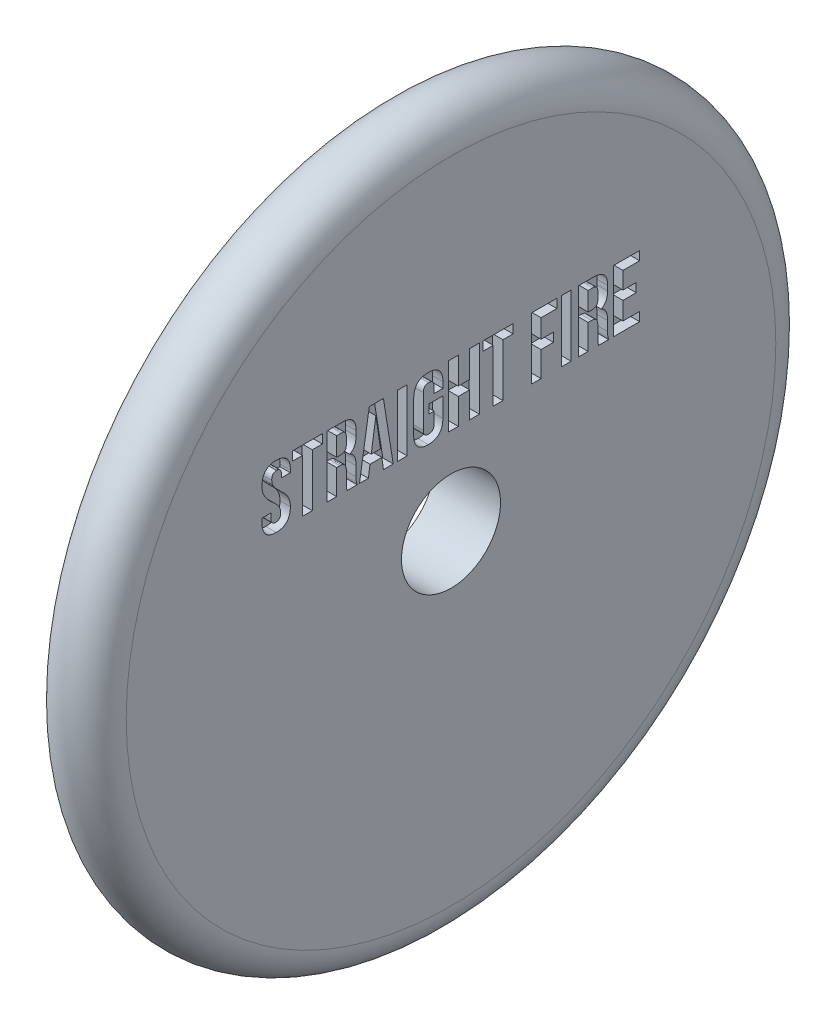
SolidWorks part; units mm, degrees
ref_plane "Front Plane" through (0, 0, 0) normal (0, 0, 1) x (1, 0, 0)
ref_plane "Top Plane" through (0, 0, 0) normal (0, 1, 0) x (1, 0, 0)
ref_plane "Right Plane" through (0, 0, 0) normal (1, 0, 0) x (0, 0, -1)
sketch "Sketch2" plane through (0, 0, 0) normal (0, 1, 0) x (1, 0, 0)
  line L0 (-9.525, 34.925) -> (9.525, 34.925) construction
  line L1 (9.525, -44.45) -> (-9.525, -44.45)
  line L2 (9.525, -44.45) -> (9.525, 34.925)
  line L3 (-9.525, -58.7375) -> (9.525, -58.7375) construction
  line L4 (-9.525, -44.45) -> (-9.525, 34.925)
  line L5 (9.525, -44.45) -> (-9.525, 44.45) construction
  line L6 (9.525, 44.45) -> (-9.525, -44.45) construction
  arc A0 (-9.525, 34.925) -> (9.525, 34.925) centre (0, 34.925) cw
  point P0 (0, 0)
  dimension "D1" = 19.05
  dimension "D2" = 88.9
  dimension "D3" = 9.525
  dimension "D4" = 14.2875
revolve "Revolve1" add sketch "Sketch2" angle 360 about L3
sketch "Sketch3" plane through (9.525, 0, 0) normal (1, 0, 0) x (0, 0, -1)
  line L0 (-148.9762, 25.0926) -> (31.5012, 25.0926) construction
  circle A1 centre (-58.7375, 0) radius 93.6625 construction
  text T0 "STRAIGHT FIRE" font "Bebas Neue" height in points 72
extrude "Cut-Extrude1" cut sketch "Sketch3" against normal blind 3
